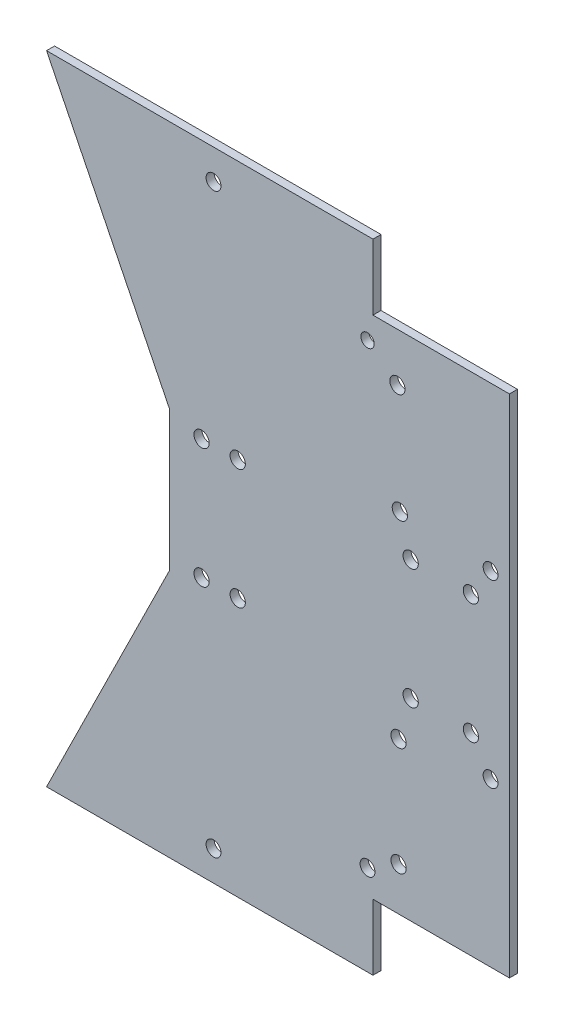
SolidWorks part; units mm, degrees
material "Thornel Mat VMA"
ref_plane "Front Plane" through (0, 0, 0) normal (0, 0, 1) x (1, 0, 0)
ref_plane "Top Plane" through (0, 0, 0) normal (0, 1, 0) x (1, 0, 0)
ref_plane "Right Plane" through (0, 0, 0) normal (1, 0, 0) x (0, 0, -1)
sketch "Sketch2" plane through (0, 0, 0) normal (0, 0, 1) x (-1, 0, 0)
  line L11 (-2.9301, 168.7083) -> (38.7094, 168.7083)
  line L12 (-2.9301, 8.6883) -> (38.7094, 8.6883)
  line L13 (38.7094, -12.1397) -> (38.7094, 8.6883)
  line L14 (143.4971, -12.1397) -> (38.7094, -12.1397)
  line L15 (38.7094, 189.5363) -> (38.7094, 168.7083)
  line L16 (143.4971, 189.5363) -> (38.7094, 189.5363)
  line L17 (104.6174, 110.8598) -> (143.4971, 189.5363)
  line L18 (104.6174, 66.5368) -> (143.4971, -12.1397)
  line L19 (104.6174, 66.5368) -> (72.8674, 66.5368)
  line L20 (72.8674, 66.5368) -> (72.8674, 110.8598)
  line L21 (104.6174, 110.8598) -> (72.8674, 110.8598)
  line L22 (-2.9301, 168.7083) -> (-2.9301, 8.6883)
  line L23 (41.9566, 19.6103) -> (41.9566, 13.2603) construction
  circle A0 centre (41.9566, 160.9613) radius 2.3495
  circle A1 centre (90.6739, 180.0113) radius 2.3495
  circle A2 centre (90.6739, -2.6147) radius 2.3495
  circle A3 centre (3.0351, 117.2098) radius 2.3495
  circle A4 centre (3.0351, 60.1868) radius 2.3495
  circle A5 centre (41.9566, 16.4353) radius 2.0955
  point P36 (41.9566, 16.4353)
  dimension "D3" = 4.699
  dimension "D7" = 31.75
  dimension "D8" = 41.6395
  dimension "D9" = 20.828
  dimension "D10" = 160.02
  dimension "D11" = 20.828
  dimension "D12" = 41.6395
  dimension "D13" = 104.7876
  dimension "D14" = 116.297
  dimension "D15" = 116.297
  dimension "D16" = 44.323
  dimension "D17" = 26.297
  dimension "D18" = 9.525
  dimension "D19" = 28.575
  dimension "D20" = 7.747
  dimension "D21" = 51.9645
  dimension "D22" = 51.4985
  dimension "D23" = 5.9651
  dimension "D24" = 51.4985
  dimension "D25" = 5.9651
  dimension "D26" = 7.747
  dimension "D27" = 3.2471
  dimension "D28" = 9.525
  dimension "D29" = 51.9645
extrude "Boss-Extrude1" add sketch "Sketch2" along normal blind 2.54
sketch "Sketch3" plane through (0, 0, 2.54) normal (0, 0, 1) x (1, 0, 0)
  line L1 (-104.6174, -66.5368) -> (-72.8674, -66.5368)
  line L2 (-104.6174, -66.5368) -> (-104.6174, -110.8598)
  line L3 (-104.6174, -110.8598) -> (-72.8674, -110.8598)
  line L4 (-72.8674, -66.5368) -> (-72.8674, -110.8598)
extrude "Boss-Extrude2" add sketch "Sketch3" against normal up to surface (2.54 mm away) up to face at (-65.9118, -88.6983, 0)
sketch "Sketch4" plane through (0, 0, 2.54) normal (0, 0, 1) x (1, 0, 0)
  line L0 (-104.6174, -66.5368) -> (-104.6174, -72.8868)
  line L1 (-104.6174, -66.5368) -> (-104.6174, -110.8598) construction
  line L2 (-104.6174, -69.7118) -> (2.9301, -69.7118) construction
  line L3 (2.9301, -168.7083) -> (2.9301, -8.6883) construction
  line L4 (-104.6174, -88.6983) -> (2.9301, -88.6983) construction
  line L5 (-104.6174, -107.6848) -> (2.9301, -107.6848) construction
  line L6 (-104.6174, -110.8598) -> (-104.6174, -104.5098)
  circle A0 centre (-94.4574, -69.7118) radius 2.413
  circle A1 centre (-83.0274, -69.7118) radius 2.413
  circle A2 centre (-28.3119, -69.7118) radius 2.413
  circle A3 centre (-9.2619, -69.7118) radius 2.413
  circle A4 centre (-9.2619, -107.6848) radius 2.413
  circle A5 centre (-28.3119, -107.6848) radius 2.413
  circle A6 centre (-83.0274, -107.6848) radius 2.413
  circle A7 centre (-94.4574, -107.6848) radius 2.413
  dimension "D2" = 10.16
  dimension "D4" = 4.826
  dimension "D5" = 4.826
  dimension "D8" = 4.826
  dimension "D9" = 4.826
  dimension "D1" = 3.175
  dimension "D3" = 11.43
  dimension "D6" = 19.05
  dimension "D7" = 12.192
extrude "Cut-Extrude1" cut sketch "Sketch4" against normal through all contours A0 | A1 | A2 | A3 | A4 | A5 | A6 | A7
sketch "Sketch5" plane through (0, 0, 2.54) normal (0, 0, 1) x (1, 0, 0)
  circle A0 centre (-31.739, -58.2731) radius 2.413
  dimension "D1" = 4.826
sketch "Sketch6" plane through (0, 0, 2.54) normal (0, 0, 1) x (1, 0, 0)
  circle A0 centre (-32.5114, -23.9918) radius 2.413
  dimension "D1" = 4.826
extrude "Cut-Extrude2" cut sketch "Sketch5" against normal through all
extrude "Cut-Extrude3" cut sketch "Sketch6" against normal through all
sketch "Sketch7" plane through (0, 0, 2.54) normal (0, 0, 1) x (1, 0, 0)
  circle A0 centre (-32.1405, -155.0714) radius 2.413
  circle A1 centre (-32.1405, -120.7814) radius 2.413
  dimension "D1" = 4.826
  dimension "D2" = 4.826
extrude "Cut-Extrude4" cut sketch "Sketch7" against normal through all
sketch "Sketch8" plane through (0, 0, 2.54) normal (0, 0, 1) x (1, 0, 0)
  line L0 (-38.7094, -168.7083) -> (2.9301, -168.7083) construction
  line L1 (-32.2387, 12.4252) -> (-40.2334, 12.4252)
  line L2 (-32.2387, 12.4252) -> (-32.2387, -8.6883)
  line L3 (-32.2387, -8.6883) -> (-40.2334, -8.6883)
  line L4 (-40.2334, 12.4252) -> (-40.2334, -8.6883)
  line L5 (-18.7398, -197.6692) -> (-40.2334, -197.6692)
  line L6 (-18.7398, -197.6692) -> (-18.7398, -168.7083)
  line L7 (-18.7398, -168.7083) -> (-40.2334, -168.7083)
  line L8 (-40.2334, -197.6692) -> (-40.2334, -168.7083)
  line L13 (-38.7094, -189.5363) -> (-38.7094, -168.7083) construction
  line L14 (2.9301, -8.6883) -> (-38.7094, -8.6883) construction
  dimension "D1" = 1.524
extrude "Cut-Extrude5" cut sketch "Sketch8" against normal through all
